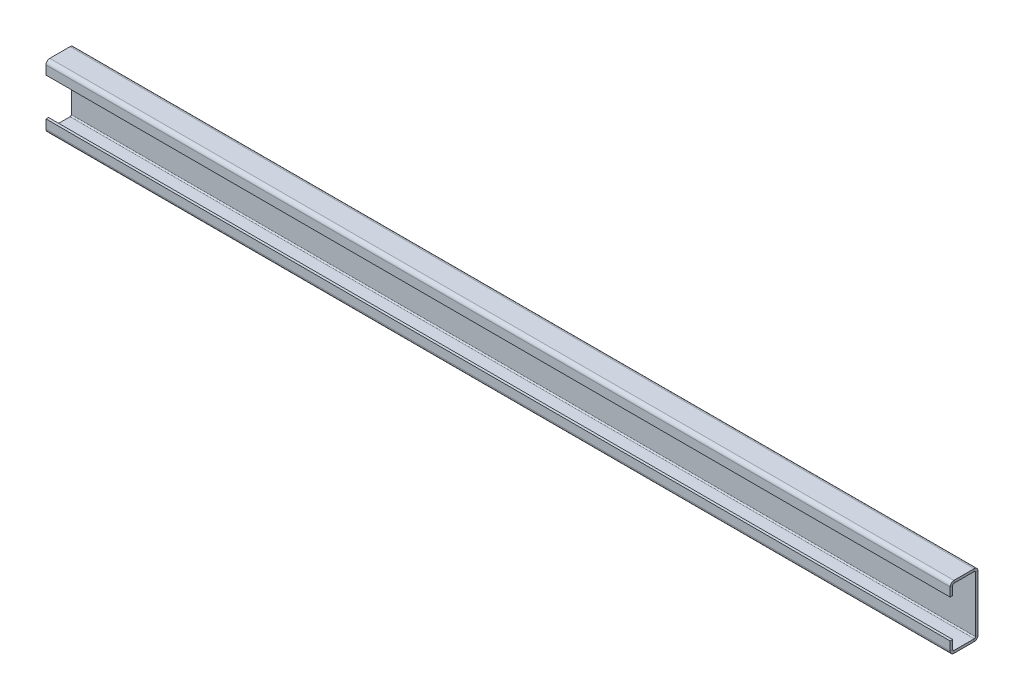
SolidWorks part; units mm, degrees
note: The reader was unsure of these and kept them because the rebuilt part matched: thickness of "Base-Flange1", "Edge-Flange1", "Edge-Flange2", "Sheet-Metal1", "Sheet-Metal2", "Sheet-Metal3"; flange length of "Edge-Flange1", "Edge-Flange2".
ref_plane "Front Plane" through (0, 0, 0) normal (0, 0, 1) x (1, 0, 0)
ref_plane "Top Plane" through (0, 0, 0) normal (0, 1, 0) x (1, 0, 0)
ref_plane "Right Plane" through (0, 0, 0) normal (1, 0, 0) x (0, 0, -1)
sketch "BaseFlange" plane through (0, 0, 0) normal (0, 0, 1) x (1, 0, 0)
  line L1 (357.5, 25) -> (-357.5, 25)
  line L2 (357.5, 25) -> (357.5, -25)
  line L3 (357.5, -25) -> (-357.5, -25)
  line L4 (-357.5, 25) -> (-357.5, -25)
  line L5 (357.5, 25) -> (-357.5, -25) construction
  line L6 (357.5, -25) -> (-357.5, 25) construction
  point P0 (0, 0)
  dimension "Width" = 715
  dimension "D2" = 50
base flange "Base-Flange1" sketch "BaseFlange" thickness 2 reverse thickness direction yes parameters "D1"=1
edge flange "Edge-Flange1" sketch "Sketch21" flange profiles "Sketch21", "Sketch23" flange angle 90 flange length 22 flange position material inside bend radius 1 thickness 2 relief rectangular parameters "D6"=10, "D8"=1
bend "EdgeBend5" bend radius 1 bend angle 90 parameters "D5"=1
bend "EdgeBend6" bend radius 1 bend angle 90 parameters "D5"=2
sketch "Sketch21" plane through (0, 25, 2) normal (0, 1, 0) x (-1, 0, 0)
  line L1 (-357.5, 0) -> (357.5, 0) construction
  line L2 (357.5, 0) -> (357.5, 20)
  line L3 (357.5, 20) -> (-357.5, 20)
  line L4 (-357.5, 20) -> (-357.5, 0)
  line L5 (-357.5, 0) -> (357.5, 0)
sketch "Sketch23" plane through (0, -25, 2) normal (0, -1, 0) x (1, 0, 0)
  line L1 (-357.5, 0) -> (357.5, 0) construction
  line L2 (357.5, 0) -> (357.5, 20)
  line L3 (357.5, 20) -> (-357.5, 20)
  line L4 (-357.5, 20) -> (-357.5, 0)
  line L5 (-357.5, 0) -> (357.5, 0)
edge flange "Edge-Flange2" sketch "Sketch25" flange profiles "Sketch25", "Sketch27" flange angle 90 flange length 10 flange position material inside bend radius 1 thickness 2 relief rectangular parameters "D6"=10, "D8"=1
bend "EdgeBend7" bend radius 1 bend angle 90 parameters "D5"=3
bend "EdgeBend8" bend radius 1 bend angle 90 parameters "D5"=4
sketch "Sketch25" plane through (0, 23, 22) normal (0, 0, -1) x (1, 0, 0)
  line L1 (357.5, 0) -> (-357.5, 0) construction
  line L2 (-357.5, 0) -> (-357.5, 8)
  line L3 (-357.5, 8) -> (357.5, 8)
  line L4 (357.5, 8) -> (357.5, 0)
  line L5 (357.5, 0) -> (-357.5, 0)
sketch "Sketch27" plane through (0, -23, 22) normal (0, 0, -1) x (-1, 0, 0)
  line L1 (357.5, 0) -> (-357.5, 0) construction
  line L2 (-357.5, 0) -> (-357.5, 8)
  line L3 (-357.5, 8) -> (357.5, 8)
  line L4 (357.5, 8) -> (357.5, 0)
  line L5 (357.5, 0) -> (-357.5, 0)
sketch "Bend-Lines1" [suppressed] plane through (0, 0, 0) normal (0, 1, 0) x (1, 0, 0)
sketch "Bounding-Box1" [suppressed] plane through (0, 0, 0) normal (0, 1, 0) x (1, 0, 0)
sheet metal parameters "Sheet-Metal1" thickness 2 parameters "D1"=1
flat pattern "Flat-Pattern1" [suppressed]
sketch "Bend-Lines2" plane through (0, 0, 0) normal (0, 1, 0) x (1, 0, 0)
sketch3d "Bounding-Box2" [suppressed]
  line L0 (-40, 950, 0) -> (-40, -950, 0) construction
  line L1 (40, 950, 0) -> (40, -950, 0) construction
  line L2 (-40, 950, 0) -> (40, 950, 0) construction
  line L3 (-40, -950, 0) -> (40, -950, 0) construction
sheet metal parameters "Sheet-Metal2" thickness 2 parameters "D1"=1
flat pattern "Flat-Pattern1"
sketch "Bend-Lines2" plane through (0, 0, 0) normal (0, 0, -1) x (-1, 0, 0)
  line L4 (-357.5, -23.2017) -> (357.5, -23.2017) construction
  line L5 (357.5, 23.2017) -> (-357.5, 23.2017) construction
  line L6 (-357.5, -23.2017) -> (357.5, -23.2017) construction
  line L7 (357.5, 23.2017) -> (-357.5, 23.2017) construction
  point P0 (355.7017, -25)
  point P1 (355.7017, 25)
  point P2 (-355.7017, 25)
  point P3 (-355.7017, -25)
sketch3d "Bounding-Box2" [suppressed]
  line L0 (357.5, -43.4033, 0) -> (-357.5, -43.4033, 0) construction
  line L1 (357.5, 43.4033, 0) -> (-357.5, 43.4033, 0) construction
  line L2 (357.5, -43.4033, 0) -> (357.5, 43.4033, 0) construction
  line L3 (-357.5, -43.4033, 0) -> (-357.5, 43.4033, 0) construction
bend of the flat pattern "Flatten-<EdgeBend5>1"
bend of the flat pattern "Flatten-<EdgeBend6>1"
sheet metal parameters "Sheet-Metal3" thickness 2 parameters "D1"=1
flat pattern "Flat-Pattern1"
sketch "Bend-Lines2" plane through (0, 0, 0) normal (0, 0, -1) x (-1, 0, 0)
  line L8 (-357.5, -41.605) -> (357.5, -41.605) construction
  line L9 (357.5, 41.605) -> (-357.5, 41.605) construction
  line L10 (-357.5, -23.2017) -> (357.5, -23.2017) construction
  line L11 (357.5, 23.2017) -> (-357.5, 23.2017) construction
  line L12 (-357.5, -41.605) -> (357.5, -41.605) construction
  line L13 (357.5, 41.605) -> (-357.5, 41.605) construction
  line L14 (-357.5, -23.2017) -> (357.5, -23.2017) construction
  line L15 (357.5, 23.2017) -> (-357.5, 23.2017) construction
sketch3d "Bounding-Box2" [suppressed]
  line L0 (357.5, -49.8066, 0) -> (-357.5, -49.8066, 0) construction
  line L1 (357.5, 49.8066, 0) -> (-357.5, 49.8066, 0) construction
  line L2 (357.5, -49.8066, 0) -> (357.5, 49.8066, 0) construction
  line L3 (-357.5, -49.8066, 0) -> (-357.5, 49.8066, 0) construction
bend of the flat pattern "Flatten-<EdgeBend6>2"
bend of the flat pattern "Flatten-<EdgeBend5>2"
bend of the flat pattern "Flatten-<EdgeBend7>1"
bend of the flat pattern "Flatten-<EdgeBend8>1"
